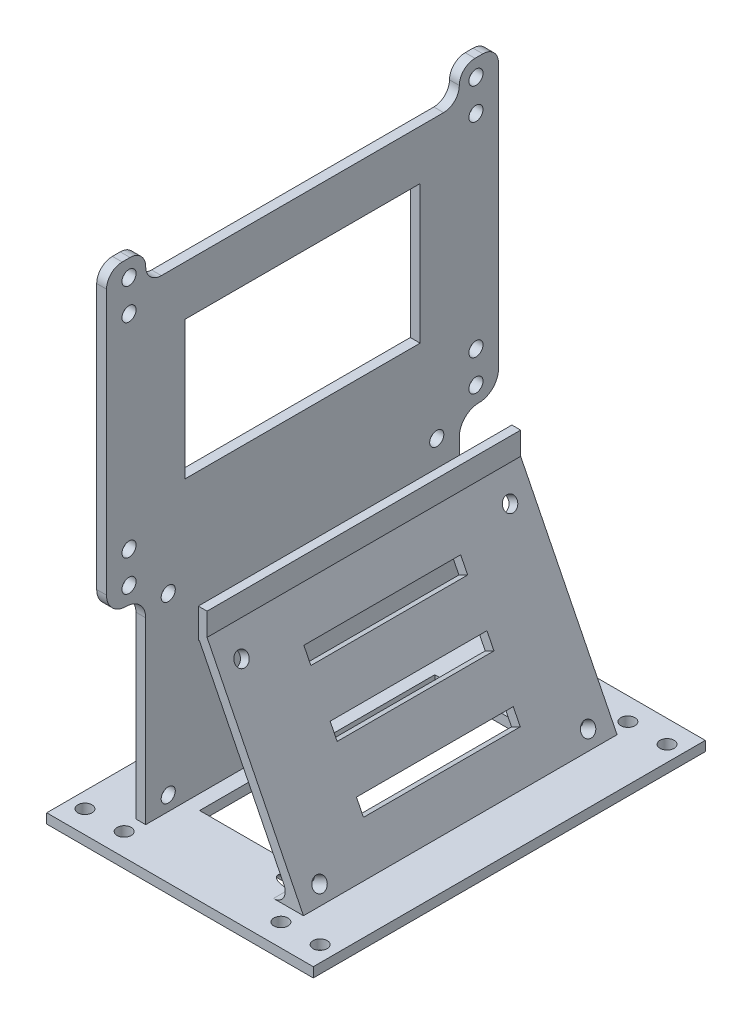
SolidWorks part; units mm, degrees
ref_plane "前视基准面" through (0, 0, 0) normal (0, 0, 1) x (1, 0, 0)
ref_plane "上视基准面" through (0, 0, 0) normal (0, 1, 0) x (1, 0, 0)
ref_plane "右视基准面" through (0, 0, 0) normal (1, 0, 0) x (0, 0, -1)
other "Configuration Table"
sketch "草图1" plane through (0, 0, 0) normal (0, 1, 0) x (1, 0, 0)
  line L0 (0, 0) -> (-30, 0) construction
  line L1 (-30, 0) -> (30, 0) construction
  line L2 (-30, 0) -> (-30, 44.25) construction
  line L3 (-30, 44.25) -> (30, 44.25) construction
  line L4 (30, 44.25) -> (30, -44.25) construction
  line L5 (30, -44.25) -> (-30, -44.25) construction
  line L6 (30, 44.25) -> (20, 44.25) construction
  line L7 (-34, 50) -> (34, 50)
  line L8 (-34, 50) -> (-34, -50)
  line L9 (-34, -50) -> (34, -50)
  line L10 (34, 50) -> (34, -50)
  line L11 (-34, 50) -> (34, -50) construction
  line L12 (-34, -50) -> (34, 50) construction
  line L13 (20, 44.25) -> (20, -44.25) construction
  line L14 (-30, 44.25) -> (-20, 44.25) construction
  line L15 (-20, 44.25) -> (-20, -44.25) construction
  circle A0 centre (-30, 44.25) radius 1.8
  circle A1 centre (30, 44.25) radius 1.8
  circle A2 centre (30, -44.25) radius 1.8
  circle A3 centre (-30, -44.25) radius 1.8
  circle A4 centre (20, -44.25) radius 1.8
  circle A5 centre (20, 44.25) radius 1.8
  circle A6 centre (-20, -44.25) radius 1.8
  circle A7 centre (-20, 44.25) radius 1.8
  dimension "D5" = 3.6
  dimension "D6" = 3.6
  dimension "D7" = 3.6
  dimension "D8" = 3.6
  dimension "D12" = 3.6
  dimension "D13" = 3.6
  dimension "D15" = 3.6
  dimension "D16" = 3.6
  dimension "D1" = 30
  dimension "D2" = 60
  dimension "D3" = 44.25
  dimension "D4" = 88.5
  dimension "D9" = 100
  dimension "D10" = 68
  dimension "D11" = 10
  dimension "D14" = 10
extrude "凸台-拉伸1" add sketch "草图1" along normal blind 2.5
sketch "草图3" plane through (0, 2.5, 0) normal (0, 1, 0) x (1, 0, 0)
  line L0 (0, 0) -> (-20, 0) construction
  line L2 (-21.25, 40) -> (-18.75, 40)
  line L3 (-21.25, 40) -> (-21.25, -40)
  line L4 (-21.25, -40) -> (-18.75, -40)
  line L5 (-18.75, 40) -> (-18.75, -40)
  line L6 (-21.25, 40) -> (-18.75, -40) construction
  line L7 (-21.25, -40) -> (-18.75, 40) construction
  dimension "D1" = 20
  dimension "D2" = 80
  dimension "D3" = 2.5
extrude "凸台-拉伸2" add sketch "草图3" along normal blind 55
sketch "草图4" plane through (0, 2.5, 0) normal (0, 1, 0) x (1, 0, 0)
  line L1 (-15, 30) -> (15, 30)
  line L2 (-15, 30) -> (-15, -30)
  line L3 (-15, -30) -> (15, -30)
  line L4 (15, 30) -> (15, -30)
  line L5 (-15, 30) -> (15, -30) construction
  line L6 (-15, -30) -> (15, 30) construction
  point P0 (0, 0)
  dimension "D1" = 60
  dimension "D2" = 30
extrude "切除-拉伸1" cut sketch "草图4" against normal blind 55
sketch "草图2" plane through (0, 0, 0) normal (0, 0, 1) x (1, 0, 0)
  line L0 (0, 2.5) -> (20, 2.5) construction
  line L1 (-34, 2.5) -> (34, 2.5) construction
  line L2 (20, 2.5) -> (20, 5.5) construction
  line L3 (20, 2.5) -> (21, 2.5) construction
  line L4 (21, 2.5) -> (22, 2.5) construction
  line L5 (21.5, 2.5) -> (20, 5.5) construction
  line L6 (20, 2.5) -> (21.5, 2.5)
  line L7 (21.5, 2.5) -> (20, 5.5)
  line L8 (20, 5.5) -> (20, 2.5)
  dimension "D1" = 20
  dimension "D2" = 3
  dimension "D3" = 1
  dimension "D4" = 1
extrude "凸台-拉伸3" add sketch "草图2" along normal blind 40 and the other way blind 40
sketch "草图5" plane through (18.2, 9.1, 0) normal (0.8944, 0.4472, 0) x (0, 0, -1)
  line L0 (0, -7.379) -> (0, 47.621) construction
  line L1 (40, -7.379) -> (-40, -7.379) construction
  line L2 (0, 47.621) -> (0, 20.121) construction
  line L4 (-40, 47.621) -> (40, 47.621)
  line L5 (-40, 47.621) -> (-40, -7.379)
  line L6 (-40, -7.379) -> (40, -7.379)
  line L7 (40, 47.621) -> (40, -7.379)
  line L8 (-40, 47.621) -> (40, -7.379) construction
  line L9 (-40, -7.379) -> (40, 47.621) construction
  dimension "D1" = 55
extrude "凸台-拉伸5" add sketch "草图5" against normal blind 2.5
sketch "草图6" plane through (-21.25, 0, 0) normal (-1, 0, 0) x (0, 0, 1)
  line L0 (0, 2.5) -> (0, 57.5) construction
  line L1 (-50, 2.5) -> (50, 2.5) construction
  line L2 (-40, 57.5) -> (40, 57.5) construction
  line L3 (0, 57.5) -> (34.25, 57.5) construction
  line L4 (34.25, 57.5) -> (-34.25, 57.5) construction
  line L5 (34.25, 57.5) -> (34.25, 52.5) construction
  line L6 (34.25, 52.5) -> (34.25, 48.9) construction
  line L7 (34.25, 50.7) -> (34.25, 6.2) construction
  line L8 (-34.25, 57.5) -> (-34.25, 52.5) construction
  line L9 (-34.25, 52.5) -> (-34.25, 48.9) construction
  line L10 (-34.25, 48.9) -> (-34.25, 4.4) construction
  line L11 (-34.25, 50.7) -> (-34.25, 6.2) construction
  circle A0 centre (34.25, 50.7) radius 1.8
  circle A1 centre (34.25, 6.2) radius 1.8
  circle A2 centre (-34.25, 50.7) radius 1.8
  circle A3 centre (-34.25, 6.2) radius 1.8
  dimension "D5" = 44.5
  dimension "D6" = 3.6
  dimension "D9" = 44.5
  dimension "D10" = 44.5
  dimension "D11" = 3.6
  dimension "D1" = 34.25
  dimension "D2" = 68.5
  dimension "D3" = 5
  dimension "D4" = 3.6
  dimension "D7" = 5
  dimension "D8" = 3.6
extrude "切除-拉伸2" cut sketch "草图6" against normal blind 2.5
sketch "草图7" plane through (18.2, 9.1, 0) normal (0.8944, 0.4472, 0) x (0, 0, -1)
  line L0 (0, 47.621) -> (34.25, 47.621) construction
  line L1 (40, 47.621) -> (-40, 47.621) construction
  line L2 (34.25, 47.621) -> (-34.25, 47.621) construction
  line L3 (-34.25, 47.621) -> (-34.25, 42.621) construction
  line L4 (-34.25, 42.621) -> (-34.25, 39.021) construction
  line L5 (-34.25, 39.021) -> (34.25, 39.021) construction
  line L6 (34.25, 39.021) -> (34.25, 42.621) construction
  line L7 (-34.25, 40.821) -> (-34.25, -3.679) construction
  line L8 (34.25, 40.821) -> (34.25, -3.679) construction
  circle A0 centre (34.25, 40.821) radius 1.8
  circle A1 centre (-34.25, 40.821) radius 1.8
  circle A2 centre (-34.25, -3.679) radius 1.8
  circle A3 centre (34.25, -3.679) radius 1.8
  dimension "D8" = 3.6
  dimension "D9" = 3.6
  dimension "D1" = 34.25
  dimension "D2" = 68.5
  dimension "D3" = 5
  dimension "D4" = 3.6
  dimension "D5" = 3.6
  dimension "D6" = 44.5
  dimension "D7" = 44.5
extrude "切除-拉伸3" cut sketch "草图7" against normal blind 2.5
sketch "草图8" plane through (0, 2.5, 0) normal (0, 1, 0) x (1, 0, 0)
  line L1 (-3.0967, 40) -> (-5.3328, 40)
  line L2 (-3.0967, 40) -> (-3.0967, -40)
  line L3 (-3.0967, -40) -> (-5.3328, -40)
  line L4 (-5.3328, 40) -> (-5.3328, -40)
  dimension "D1" = 80
  dimension "D2" = 2.2361
extrude "凸台-拉伸6" add sketch "草图8" against normal blind 7.5 from surface at 55 starting at face at (-20, 57.5, 0)
sketch "草图10" plane through (-21.25, 0, 0) normal (-1, 0, 0) x (0, 0, 1)
  line L0 (0, 57.5) -> (0, 117.5) construction
  line L1 (-40, 57.5) -> (40, 57.5) construction
  line L2 (0, 117.5) -> (44.25, 117.5) construction
  line L3 (44.25, 117.5) -> (44.25, 57.5) construction
  line L4 (44.25, 57.5) -> (-44.25, 57.5) construction
  line L5 (-44.25, 57.5) -> (-44.25, 117.5) construction
  line L6 (-40, 57.5) -> (-40, 2.5) construction
  line L7 (-50, 120.5) -> (50, 120.5)
  line L8 (-50, 120.5) -> (-50, 54.5)
  line L9 (-50, 54.5) -> (50, 54.5)
  line L10 (50, 120.5) -> (50, 54.5)
  line L11 (-50, 120.5) -> (50, 54.5) construction
  line L12 (-50, 54.5) -> (50, 120.5) construction
  line L13 (-50, 120.5) -> (50, 120.5)
  line L14 (-50, 120.5) -> (-50, 121.8)
  line L15 (-50, 121.8) -> (50, 121.8)
  line L16 (50, 120.5) -> (50, 121.8)
  line L17 (-50, 54.5) -> (-40, 54.5)
  line L18 (-50, 54.5) -> (-50, 53.2)
  line L19 (-50, 53.2) -> (-40, 53.2)
  line L20 (-40, 54.5) -> (-40, 53.2)
  line L21 (40, 57.5) -> (40, 2.5) construction
  line L22 (50, 54.5) -> (40, 54.5)
  line L23 (50, 54.5) -> (50, 53.2)
  line L24 (50, 53.2) -> (40, 53.2)
  line L25 (40, 54.5) -> (40, 53.2)
  circle A0 centre (44.25, 117.5) radius 1.8
  circle A1 centre (44.25, 57.5) radius 1.8
  circle A2 centre (-44.25, 57.5) radius 1.8
  circle A3 centre (-44.25, 117.5) radius 1.8
  point P13 (0, 87.5)
  line M10 (40, 2.5) -> (40, 57.5)
  line M11 (40, 57.5) -> (-40, 57.5)
  line M12 (-40, 57.5) -> (-40, 2.5)
  dimension "D5" = 3.6
  dimension "D6" = 3.6
  dimension "D7" = 3.6
  dimension "D8" = 3.6
  dimension "D1" = 60
  dimension "D2" = 44.25
  dimension "D3" = 60
  dimension "D4" = 88.5
  dimension "D9" = 66
  dimension "D10" = 100
  dimension "D11" = 1.3
  dimension "D12" = 100
  dimension "D13" = 1.3
  dimension "D14" = 1.3
extrude "凸台-拉伸7" add sketch "草图10" against normal up to surface (2.5 mm away) contours L10 L7 L8 L9 A3 A2 A1 A0 M12 M11 M10 | L9 M12 M10 M11 | L18 L19 L9 M12 | L24 L23 L9 M10 | L7 L16 L15 L14 up to face at (-18.75, 6.2, 36.05)
fillet "圆角1" radius 5 6 edges at (-20, 121.8, -50) (-20, 121.8, 50) (-20, 53.2, 50) (-20, 53.2, -50) (-20, 53.2, -40) (-20, 53.2, 40)
fillet "圆角4" radius 3 1 edges at (18.7049, 2.5, 0)
sketch "草图11" plane through (18.2, 9.1, 0) normal (0.8944, 0.4472, 0) x (0, 0, -1)
  circle A0 centre (-34.25, -3.679) radius 1.8
  circle A1 centre (34.25, -3.679) radius 1.8
extrude "切除-拉伸4" cut sketch "草图11" against normal blind 30
sketch "草图12" plane through (0, 57.5, 0) normal (0, 1, 0) x (1, 0, 0)
  line L0 (-3.0967, 0) -> (-3.0967, -20) construction
  line L1 (-3.0967, 40) -> (-3.0967, -40) construction
  line L3 (-3.0967, -20) -> (-18.75, -20)
  line L4 (-3.0967, -20) -> (-3.0967, -16)
  line L5 (-3.0967, -16) -> (-18.75, -16)
  line L6 (-18.75, -20) -> (-18.75, -16)
  line L7 (-18.75, -45) -> (-18.75, 45) construction
  line L8 (-3.0967, 0) -> (-3.0967, 20) construction
  line L9 (-3.0967, 20) -> (-19.6467, 20)
  line L10 (-3.0967, 20) -> (-3.0967, 16)
  line L11 (-3.0967, 16) -> (-19.6467, 16)
  line L12 (-19.6467, 20) -> (-19.6467, 16)
  dimension "D1" = 20
  dimension "D2" = 4
  dimension "D3" = 15.6533
  dimension "D4" = 20
  dimension "D5" = 4
  dimension "D6" = 16.55
sketch "草图13" plane through (18.2, 9.1, 0) normal (0.8944, 0.4472, 0) x (0, 0, -1)
  line L0 (0, 47.621) -> (0, -7.379) construction
  line L1 (40, 47.621) -> (-40, 47.621) construction
  line L2 (40, -7.379) -> (-40, -7.379) construction
  line L3 (0, 20.121) -> (0, 35.121) construction
  line L4 (-20, 22.121) -> (20, 22.121)
  line L5 (-20, 22.121) -> (-20, 18.121)
  line L6 (-20, 18.121) -> (20, 18.121)
  line L7 (20, 22.121) -> (20, 18.121)
  line L8 (-20, 22.121) -> (20, 18.121) construction
  line L9 (-20, 18.121) -> (20, 22.121) construction
  line L10 (0, 35.121) -> (0, 5.121) construction
  line L12 (-20, 37.121) -> (20, 37.121)
  line L13 (-20, 37.121) -> (-20, 33.121)
  line L14 (-20, 33.121) -> (20, 33.121)
  line L15 (20, 37.121) -> (20, 33.121)
  line L16 (-20, 37.121) -> (20, 33.121) construction
  line L17 (-20, 33.121) -> (20, 37.121) construction
  line L18 (-20, 7.121) -> (20, 7.121)
  line L19 (-20, 7.121) -> (-20, 3.121)
  line L20 (-20, 3.121) -> (20, 3.121)
  line L21 (20, 7.121) -> (20, 3.121)
  line L22 (-20, 7.121) -> (20, 3.121) construction
  line L23 (-20, 3.121) -> (20, 7.121) construction
  point P6 (0, 20.121)
  dimension "D1" = 4
  dimension "D2" = 40
  dimension "D3" = 15
  dimension "D4" = 30
  dimension "D5" = 4
  dimension "D6" = 40
  dimension "D7" = 4
  dimension "D8" = 40
extrude "切除-拉伸5" cut sketch "草图13" against normal blind 2.5
sketch "草图14" plane through (-21.25, 0, 0) normal (-1, 0, 0) x (0, 0, 1)
  line L0 (-44.25, 57.5) -> (-44.25, 65.5) construction
  line L1 (44.25, 57.5) -> (44.25, 65.5) construction
  circle A0 centre (-44.25, 65.5) radius 1.8
  circle A1 centre (44.25, 65.5) radius 1.8
  dimension "D2" = 3.6
  dimension "D4" = 3.6
  dimension "D1" = 8
  dimension "D3" = 8
extrude "切除-拉伸6" cut sketch "草图14" against normal blind 2.5
sketch "草图15" plane through (-21.25, 0, 0) normal (-1, 0, 0) x (0, 0, 1)
  line L0 (-44.25, 117.5) -> (-44.25, 125.5) construction
  line L1 (44.25, 117.5) -> (44.25, 125.5) construction
  line L2 (0, 121.8) -> (-40, 121.8) construction
  line L3 (-45, 121.8) -> (45, 121.8) construction
  line L4 (-40, 121.8) -> (40, 121.8) construction
  line L5 (-50, 121.8) -> (-50, 114.7602) construction
  line L6 (40, 121.8) -> (50, 121.8)
  line L7 (40, 121.8) -> (40, 129.8)
  line L8 (40, 129.8) -> (50, 129.8)
  line L9 (50, 121.8) -> (50, 129.8)
  line L10 (-40, 121.8) -> (-50, 121.8)
  line L11 (-40, 121.8) -> (-40, 129.8)
  line L12 (-40, 129.8) -> (-50, 129.8)
  line L13 (-50, 121.8) -> (-50, 129.8)
  line L14 (-50, 116.8) -> (-50, 58.2) construction
  line L15 (-50, 114.7602) -> (-42.9602, 121.8) construction
  line L16 (-42.9602, 121.8) -> (-50, 121.8) construction
  line L17 (-50, 121.8) -> (-50, 114.7602)
  line L18 (-50, 114.7602) -> (-42.9602, 121.8)
  line L19 (-42.9602, 121.8) -> (-50, 121.8)
  line L20 (50, 121.8) -> (50, 115.4562)
  line L21 (50, 116.8) -> (50, 58.2) construction
  line L22 (50, 115.4562) -> (44.25, 121.8)
  line L23 (44.25, 121.8) -> (50, 121.8)
  circle A0 centre (44.25, 125.5) radius 1.8
  circle A1 centre (-44.25, 125.5) radius 1.8
  dimension "D3" = 3.6
  dimension "D4" = 3.6
  dimension "D1" = 8
  dimension "D2" = 8
  dimension "D5" = 40
  dimension "D6" = 80
  dimension "D7" = 8
  dimension "D8" = 10
  dimension "D9" = 8
  dimension "D10" = 10
extrude "凸台-拉伸10" add sketch "草图15" against normal blind 2.5 contours L6 L9 L8 L7 L2 A0 | L22 L12 L13 L2 | L20 L6 L13 | L10 L17 L3 | L4 L18 L10 L3 | L13 L10 L2 L11 L12 A1
fillet "圆角6" radius 4 10 edges at (-18.75, 125.8, 40) (-21.25, 125.8, 40) (-20, 121.8, 40) (-20, 129.8, 40) (-20, 129.8, 50) (-21.25, 125.8, -40) (-20, 129.8, -50) (-18.75, 125.8, -40) (-20, 129.8, -40) (-20, 121.8, -40)
sketch "草图16" plane through (-21.25, 0, 0) normal (-1, 0, 0) x (0, 0, 1)
  line L0 (-44.25, 117.5) -> (44.25, 65.5) construction
  line L1 (44.25, 65.5) -> (0, 91.5) construction
  line L3 (-30, 109.1271) -> (30, 109.1271)
  line L4 (-30, 109.1271) -> (-30, 73.8729)
  line L5 (-30, 73.8729) -> (30, 73.8729)
  line L6 (30, 109.1271) -> (30, 73.8729)
  line L7 (-30, 109.1271) -> (30, 73.8729) construction
  line L8 (-30, 73.8729) -> (30, 109.1271) construction
  dimension "D1" = 35.2542
  dimension "D2" = 60
extrude "切除-拉伸8" cut sketch "草图16" against normal blind 10
